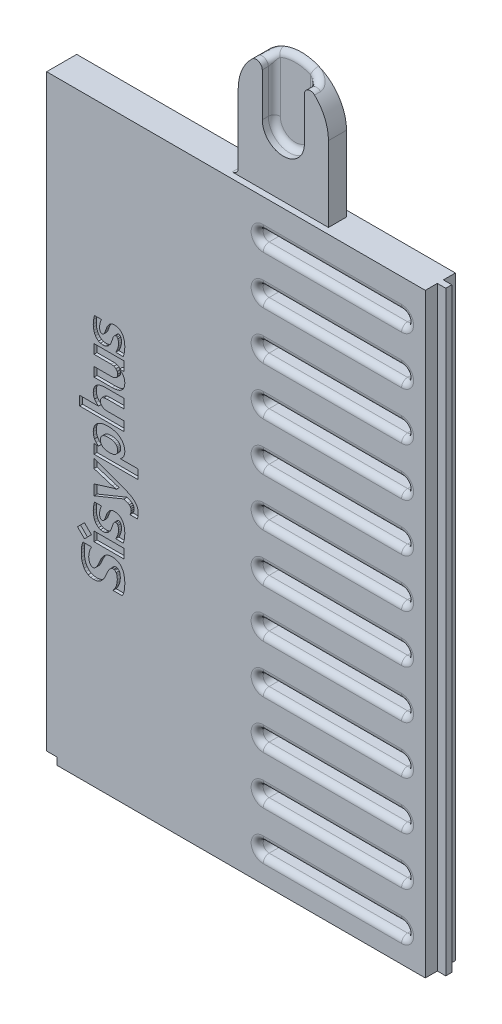
SolidWorks part; units mm, degrees
material "PVC Rigid"
ref_plane "Front Plane" through (0, 0, 0) normal (0, 0, 1) x (1, 0, 0)
ref_plane "Top Plane" through (0, 0, 0) normal (0, 1, 0) x (1, 0, 0)
ref_plane "Right Plane" through (0, 0, 0) normal (1, 0, 0) x (0, 0, -1)
sketch "Sketch1" plane through (0, 0, 0) normal (0, 1, 0) x (1, 0, 0)
  line L1 (-38.35, 2.5) -> (38.35, 2.5)
  line L2 (-38.35, 2.5) -> (-38.35, -2.5)
  line L3 (-38.35, -2.5) -> (38.35, -2.5)
  line L4 (38.35, 2.5) -> (38.35, -2.5)
  line L5 (-38.35, 2.5) -> (38.35, -2.5) construction
  line L6 (-38.35, -2.5) -> (38.35, 2.5) construction
  point P0 (0, 0)
  dimension "D1" = 5
  dimension "D2" = 76.7
extrude "Boss-Extrude1" add sketch "Sketch1" along normal blind 99
sketch "Sketch2" plane through (0, 99, 0) normal (0, 1, 0) x (1, 0, 0)
  line L0 (-7.5, -1.5) -> (-7.5, -0.5)
  line L1 (-6.5, 1.5) -> (7.5, 1.5)
  line L2 (-7.5, 0.5) -> (-7.5, -0.5)
  line L3 (-6.5, -1.5) -> (7.5, -1.5)
  line L5 (-7.5, 1.5) -> (7.5, -1.5) construction
  line L6 (-7.5, -1.5) -> (7.5, 1.5) construction
  line L7 (-7.5, 1.5) -> (-6.5, 1.5)
  line L8 (-7.5, -1.5) -> (-6.5, -1.5)
  line L9 (7.5, 1.5) -> (7.5, -1.5)
  line L12 (-7.5, 0.5) -> (-7.5, 1.5)
  point P0 (0, 0)
  dimension "D1" = 15
  dimension "D2" = 3
extrude "Boss-Extrude2" add sketch "Sketch2" along normal blind 20
sketch "Sketch3" plane through (0, 0, 1.5) normal (0, 0, 1) x (1, 0, 0)
  line L0 (-7.5, 119) -> (7.5, 119) construction
  line L1 (-3.5, 119) -> (3.5, 119)
  line L2 (-3.5, 119) -> (-3.5, 109)
  line L4 (3.5, 119) -> (3.5, 109)
  line L5 (-7.5, 119) -> (-7.5, 99) construction
  arc A0 (-3.5, 109) -> (3.5, 109) centre (0, 109) ccw
  dimension "D3" = 7.5
  dimension "D1" = 7
  dimension "D2" = 10
fillet "Fillet2" radius 1 1 edges at (-7.5, 99, 0)
sketch "Sketch4" plane through (0, 99, 0) normal (0, 1, 0) x (1, 0, 0)
  line L4 (-36.15, 0.5653) -> (-38.65, 0.5653)
  line L5 (-36.15, -1.4347) -> (-36.15, 0.5653)
  line L6 (-38.65, -1.4347) -> (-36.15, -1.4347)
  line L7 (-38.65, 0.5653) -> (-38.65, -1.4347)
  line L8 (-36.15, 0.5653) -> (-38.65, 0.5653)
  line L9 (-36.15, -1.4347) -> (-36.15, 0.5653)
  line L10 (-38.65, -1.4347) -> (-36.15, -1.4347)
  line L11 (-38.65, 0.5653) -> (-38.65, -1.4347)
  dimension "D1" = 0
sketch "Sketch5" plane through (0, 0, 0) normal (0, 0, 1) x (1, 0, 0)
  line L1 (24.6, -5) -> (60, -5)
  line L2 (24.6, -5) -> (24.6, 130)
  line L3 (24.6, 130) -> (60, 130)
  line L4 (60, -5) -> (60, 130)
extrude "Trim_door_beside_fixed_buttons" cut sketch "Sketch5" along normal blind 20 from offset 10 offset against normal yes
sketch "Sketch6" plane through (0, 0, 0) normal (0, 0, 1) x (1, 0, 0)
  line L0 (-39, -1) -> (-36.6, -1)
  line L1 (-36.6, -1) -> (-36.6, 1.2)
  line L2 (-36.6, 1.2) -> (-39, 1.2)
  line L3 (-39, 1.2) -> (-39, -1)
extrude "Clear_original_end_corner" cut sketch "Sketch6" along normal blind 10 from offset 5 offset against normal yes
sketch "Sketch8" plane through (0, 0, 0) normal (0, 0, 1) x (1, 0, 0)
  line L0 (24, 0) -> (26, 0)
  line L1 (26, 0) -> (26, 99)
  line L2 (26, 99) -> (24, 99)
  line L3 (24, 99) -> (24, 0)
extrude "Dust_overlap_tongue" add sketch "Sketch8" along normal blind 1 from offset 0.5 offset against normal yes
sketch "Sketch11" plane through (0, 0, 0) normal (0, 0, 1) x (1, 0, 0)
  line L0 (-4.6719, 20) -> (-5.7969, 19.8938)
  line L1 (-5.7969, 19.8938) -> (-5.9531, 20.3813)
  line L2 (-5.9531, 20.3813) -> (-6.2094, 20.725)
  line L3 (-6.2094, 20.725) -> (-6.5719, 20.925)
  line L4 (-6.5719, 20.925) -> (-7.0469, 20.9875)
  line L5 (-7.0469, 20.9875) -> (-7.5344, 20.9313)
  line L6 (-7.5344, 20.9313) -> (-7.8844, 20.75)
  line L7 (-7.8844, 20.75) -> (-8.1031, 20.4938)
  line L8 (-8.1031, 20.4938) -> (-8.1719, 20.2)
  line L9 (-8.1719, 20.2) -> (-8.1406, 20.0125)
  line L10 (-8.1406, 20.0125) -> (-8.0531, 19.8563)
  line L11 (-8.0531, 19.8563) -> (-7.8906, 19.7188)
  line L12 (-7.8906, 19.7188) -> (-7.6344, 19.6063)
  line L13 (-7.6344, 19.6063) -> (-7.4969, 19.5625)
  line L14 (-7.4969, 19.5625) -> (-7.3031, 19.5063)
  line L15 (-7.3031, 19.5063) -> (-7.0406, 19.4375)
  line L16 (-7.0406, 19.4375) -> (-6.7094, 19.3563)
  line L17 (-6.7094, 19.3563) -> (-6.2781, 19.2313)
  line L18 (-6.2781, 19.2313) -> (-5.9156, 19.1)
  line L19 (-5.9156, 19.1) -> (-5.6281, 18.95)
  line L20 (-5.6281, 18.95) -> (-5.4031, 18.7875)
  line L21 (-5.4031, 18.7875) -> (-5.1719, 18.5375)
  line L22 (-5.1719, 18.5375) -> (-5.0094, 18.2625)
  line L23 (-5.0094, 18.2625) -> (-4.9094, 17.9625)
  line L24 (-4.9094, 17.9625) -> (-4.8781, 17.6375)
  line L25 (-4.8781, 17.6375) -> (-4.9406, 17.2125)
  line L26 (-4.9406, 17.2125) -> (-5.1281, 16.8188)
  line L27 (-5.1281, 16.8188) -> (-5.4281, 16.4813)
  line L28 (-5.4281, 16.4813) -> (-5.8406, 16.2375)
  line L29 (-5.8406, 16.2375) -> (-6.3594, 16.0875)
  line L30 (-6.3594, 16.0875) -> (-6.9656, 16.0375)
  line L31 (-6.9656, 16.0375) -> (-7.4719, 16.0688)
  line L32 (-7.4719, 16.0688) -> (-7.9094, 16.1563)
  line L33 (-7.9094, 16.1563) -> (-8.2844, 16.3063)
  line L34 (-8.2844, 16.3063) -> (-8.5906, 16.5125)
  line L35 (-8.5906, 16.5125) -> (-8.8281, 16.7688)
  line L36 (-8.8281, 16.7688) -> (-9.0094, 17.0625)
  line L37 (-9.0094, 17.0625) -> (-9.1156, 17.4)
  line L38 (-9.1156, 17.4) -> (-9.1594, 17.775)
  line L39 (-9.1594, 17.775) -> (-8.0031, 17.825)
  line L40 (-8.0031, 17.825) -> (-7.8906, 17.4438)
  line L41 (-7.8906, 17.4438) -> (-7.6906, 17.1875)
  line L42 (-7.6906, 17.1875) -> (-7.3781, 17.0438)
  line L43 (-7.3781, 17.0438) -> (-6.9531, 16.9938)
  line L44 (-6.9531, 16.9938) -> (-6.5094, 17.05)
  line L45 (-6.5094, 17.05) -> (-6.1656, 17.2063)
  line L46 (-6.1656, 17.2063) -> (-6.0281, 17.3625)
  line L47 (-6.0281, 17.3625) -> (-5.9844, 17.5563)
  line L48 (-5.9844, 17.5563) -> (-6.0281, 17.75)
  line L49 (-6.0281, 17.75) -> (-6.1531, 17.9063)
  line L50 (-6.1531, 17.9063) -> (-6.3031, 18)
  line L51 (-6.3031, 18) -> (-6.5281, 18.0938)
  line L52 (-6.5281, 18.0938) -> (-6.8344, 18.1875)
  line L53 (-6.8344, 18.1875) -> (-7.2156, 18.2875)
  line L54 (-7.2156, 18.2875) -> (-7.6094, 18.3938)
  line L55 (-7.6094, 18.3938) -> (-7.9531, 18.4938)
  line L56 (-7.9531, 18.4938) -> (-8.2344, 18.6)
  line L57 (-8.2344, 18.6) -> (-8.4656, 18.7)
  line L58 (-8.4656, 18.7) -> (-8.8281, 18.9563)
  line L59 (-8.8281, 18.9563) -> (-9.0969, 19.2813)
  line L60 (-9.0969, 19.2813) -> (-9.2719, 19.6938)
  line L61 (-9.2719, 19.6938) -> (-9.3281, 20.1938)
  line L62 (-9.3281, 20.1938) -> (-9.2594, 20.675)
  line L63 (-9.2594, 20.675) -> (-9.0531, 21.1188)
  line L64 (-9.0531, 21.1188) -> (-8.7219, 21.4938)
  line L65 (-8.7219, 21.4938) -> (-8.2781, 21.7563)
  line L66 (-8.2781, 21.7563) -> (-7.7156, 21.9125)
  line L67 (-7.7156, 21.9125) -> (-7.0344, 21.9625)
  line L68 (-7.0344, 21.9625) -> (-6.5219, 21.9313)
  line L69 (-6.5219, 21.9313) -> (-6.0719, 21.8375)
  line L70 (-6.0719, 21.8375) -> (-5.6906, 21.6813)
  line L71 (-5.6906, 21.6813) -> (-5.3656, 21.4625)
  line L72 (-5.3656, 21.4625) -> (-5.1031, 21.1875)
  line L73 (-5.1031, 21.1875) -> (-4.9031, 20.85)
  line L74 (-4.9031, 20.85) -> (-4.7594, 20.4563)
  line L75 (-4.7594, 20.4563) -> (-4.6719, 20)
  line L76 (-6.4512, 25.1523) -> (-6.4512, 24.1367)
  line L77 (-6.4512, 24.1367) -> (-7.5488, 24.1367)
  line L78 (-7.5488, 24.1367) -> (-7.5488, 25.1523)
  line L79 (-7.5488, 25.1523) -> (-6.4512, 25.1523)
  line L80 (-6.4512, 29.8633) -> (-6.4512, 25.7148)
  line L81 (-6.4512, 25.7148) -> (-7.5488, 25.7148)
  line L82 (-7.5488, 25.7148) -> (-7.5488, 29.8633)
  line L83 (-7.5488, 29.8633) -> (-6.4512, 29.8633)
  line L84 (-5.0625, 35.8938) -> (-6.1687, 35.725)
  line L85 (-6.1687, 35.725) -> (-6.275, 36.0062)
  line L86 (-6.275, 36.0062) -> (-6.45, 36.2125)
  line L87 (-6.45, 36.2125) -> (-6.7062, 36.3313)
  line L88 (-6.7062, 36.3313) -> (-7.0562, 36.375)
  line L89 (-7.0562, 36.375) -> (-7.425, 36.3375)
  line L90 (-7.425, 36.3375) -> (-7.6937, 36.2188)
  line L91 (-7.6937, 36.2188) -> (-7.8062, 36.0938)
  line L92 (-7.8062, 36.0938) -> (-7.8375, 35.925)
  line L93 (-7.8375, 35.925) -> (-7.7625, 35.7188)
  line L94 (-7.7625, 35.7188) -> (-7.625, 35.6438)
  line L95 (-7.625, 35.6438) -> (-7.3937, 35.575)
  line L96 (-7.3937, 35.575) -> (-6.7875, 35.4313)
  line L97 (-6.7875, 35.4313) -> (-6.3125, 35.2937)
  line L98 (-6.3125, 35.2937) -> (-5.95, 35.1625)
  line L99 (-5.95, 35.1625) -> (-5.7125, 35.0437)
  line L100 (-5.7125, 35.0437) -> (-5.4937, 34.8562)
  line L101 (-5.4937, 34.8562) -> (-5.3438, 34.6438)
  line L102 (-5.3438, 34.6438) -> (-5.25, 34.3875)
  line L103 (-5.25, 34.3875) -> (-5.2188, 34.1062)
  line L104 (-5.2188, 34.1062) -> (-5.2437, 33.85)
  line L105 (-5.2437, 33.85) -> (-5.325, 33.6125)
  line L106 (-5.325, 33.6125) -> (-5.4562, 33.3938)
  line L107 (-5.4562, 33.3938) -> (-5.6437, 33.2)
  line L108 (-5.6437, 33.2) -> (-5.8875, 33.0375)
  line L109 (-5.8875, 33.0375) -> (-6.1875, 32.925)
  line L110 (-6.1875, 32.925) -> (-6.5437, 32.8563)
  line L111 (-6.5437, 32.8563) -> (-6.9625, 32.8313)
  line L112 (-6.9625, 32.8313) -> (-7.3625, 32.85)
  line L113 (-7.3625, 32.85) -> (-7.7062, 32.9)
  line L114 (-7.7062, 32.9) -> (-8, 32.9875)
  line L115 (-8, 32.9875) -> (-8.2313, 33.1125)
  line L116 (-8.2313, 33.1125) -> (-8.5812, 33.4563)
  line L117 (-8.5812, 33.4563) -> (-8.8, 33.9313)
  line L118 (-8.8, 33.9313) -> (-7.7625, 34.125)
  line L119 (-7.7625, 34.125) -> (-7.6687, 33.9125)
  line L120 (-7.6687, 33.9125) -> (-7.5125, 33.75)
  line L121 (-7.5125, 33.75) -> (-7.2875, 33.6563)
  line L122 (-7.2875, 33.6563) -> (-6.9812, 33.625)
  line L123 (-6.9812, 33.625) -> (-6.6125, 33.6563)
  line L124 (-6.6125, 33.6563) -> (-6.3625, 33.7438)
  line L125 (-6.3625, 33.7438) -> (-6.2687, 33.8438)
  line L126 (-6.2687, 33.8438) -> (-6.2375, 33.9688)
  line L127 (-6.2375, 33.9688) -> (-6.2625, 34.075)
  line L128 (-6.2625, 34.075) -> (-6.3438, 34.1687)
  line L129 (-6.3438, 34.1687) -> (-6.4625, 34.225)
  line L130 (-6.4625, 34.225) -> (-6.675, 34.3)
  line L131 (-6.675, 34.3) -> (-6.9812, 34.3812)
  line L132 (-6.9812, 34.3812) -> (-7.375, 34.475)
  line L133 (-7.375, 34.475) -> (-7.7812, 34.5813)
  line L134 (-7.7812, 34.5813) -> (-8.1187, 34.6937)
  line L135 (-8.1187, 34.6937) -> (-8.3875, 34.825)
  line L136 (-8.3875, 34.825) -> (-8.5938, 34.9625)
  line L137 (-8.5938, 34.9625) -> (-8.7437, 35.125)
  line L138 (-8.7437, 35.125) -> (-8.85, 35.3125)
  line L139 (-8.85, 35.3125) -> (-8.9187, 35.5312)
  line L140 (-8.9187, 35.5312) -> (-8.9375, 35.7812)
  line L141 (-8.9375, 35.7812) -> (-8.9062, 36.0563)
  line L142 (-8.9062, 36.0563) -> (-8.8187, 36.3125)
  line L143 (-8.8187, 36.3125) -> (-8.6688, 36.5438)
  line L144 (-8.6688, 36.5438) -> (-8.4625, 36.7625)
  line L145 (-8.4625, 36.7625) -> (-8.1937, 36.9375)
  line L146 (-8.1937, 36.9375) -> (-7.875, 37.0687)
  line L147 (-7.875, 37.0687) -> (-7.4937, 37.1438)
  line L148 (-7.4937, 37.1438) -> (-7.0562, 37.1688)
  line L149 (-7.0562, 37.1688) -> (-6.65, 37.15)
  line L150 (-6.65, 37.15) -> (-6.2937, 37.0813)
  line L151 (-6.2937, 37.0813) -> (-5.9812, 36.975)
  line L152 (-5.9812, 36.975) -> (-5.7125, 36.825)
  line L153 (-5.7125, 36.825) -> (-5.4875, 36.6375)
  line L154 (-5.4875, 36.6375) -> (-5.3063, 36.425)
  line L155 (-5.3063, 36.425) -> (-5.1625, 36.175)
  line L156 (-5.1625, 36.175) -> (-5.0625, 35.8938)
  line L157 (-4.8656, 40.0813) -> (-6.0344, 40.0813)
  line L158 (-6.0344, 40.0813) -> (-7.0281, 43.0312)
  line L159 (-7.0281, 43.0312) -> (-7.9969, 40.0813)
  line L160 (-7.9969, 40.0813) -> (-9.1344, 40.0813)
  line L161 (-9.1344, 40.0813) -> (-7.6656, 44.075)
  line L162 (-7.6656, 44.075) -> (-7.4031, 44.8)
  line L163 (-7.4031, 44.8) -> (-7.2656, 45.1187)
  line L164 (-7.2656, 45.1187) -> (-7.1281, 45.3562)
  line L165 (-7.1281, 45.3562) -> (-6.9906, 45.5312)
  line L166 (-6.9906, 45.5312) -> (-6.8281, 45.6625)
  line L167 (-6.8281, 45.6625) -> (-6.6406, 45.7688)
  line L168 (-6.6406, 45.7688) -> (-6.4094, 45.85)
  line L169 (-6.4094, 45.85) -> (-5.8531, 45.9187)
  line L170 (-5.8531, 45.9187) -> (-5.2281, 45.85)
  line L171 (-5.2281, 45.85) -> (-5.1344, 44.9875)
  line L172 (-5.1344, 44.9875) -> (-5.5969, 45.0437)
  line L173 (-5.5969, 45.0437) -> (-5.9281, 44.9875)
  line L174 (-5.9281, 44.9875) -> (-6.1656, 44.8187)
  line L175 (-6.1656, 44.8187) -> (-6.3281, 44.5625)
  line L176 (-6.3281, 44.5625) -> (-6.4469, 44.2438)
  line L177 (-6.4469, 44.2438) -> (-4.8656, 40.0813)
  line L178 (-4.975, 48.1813) -> (-6, 48.1813)
  line L179 (-6, 48.1813) -> (-6, 48.7938)
  line L180 (-6, 48.7938) -> (-6.2313, 48.5125)
  line L181 (-6.2313, 48.5125) -> (-6.5375, 48.2875)
  line L182 (-6.5375, 48.2875) -> (-6.9, 48.1375)
  line L183 (-6.9, 48.1375) -> (-7.2938, 48.0875)
  line L184 (-7.2938, 48.0875) -> (-7.6438, 48.125)
  line L185 (-7.6438, 48.125) -> (-7.9625, 48.2313)
  line L186 (-7.9625, 48.2313) -> (-8.25, 48.4062)
  line L187 (-8.25, 48.4062) -> (-8.5187, 48.6562)
  line L188 (-8.5187, 48.6562) -> (-8.7375, 48.9688)
  line L189 (-8.7375, 48.9688) -> (-8.9, 49.3375)
  line L190 (-8.9, 49.3375) -> (-8.9938, 49.7562)
  line L191 (-8.9938, 49.7562) -> (-9.025, 50.2375)
  line L192 (-9.025, 50.2375) -> (-8.9938, 50.725)
  line L193 (-8.9938, 50.725) -> (-8.9, 51.1562)
  line L194 (-8.9, 51.1562) -> (-8.7375, 51.5312)
  line L195 (-8.7375, 51.5312) -> (-8.5187, 51.85)
  line L196 (-8.5187, 51.85) -> (-8.25, 52.1)
  line L197 (-8.25, 52.1) -> (-7.9563, 52.2812)
  line L198 (-7.9563, 52.2812) -> (-7.6375, 52.3875)
  line L199 (-7.6375, 52.3875) -> (-7.2875, 52.425)
  line L200 (-7.2875, 52.425) -> (-6.9563, 52.3938)
  line L201 (-6.9563, 52.3938) -> (-6.6625, 52.2875)
  line L202 (-6.6625, 52.2875) -> (-6.375, 52.1062)
  line L203 (-6.375, 52.1062) -> (-6.075, 51.8187)
  line L204 (-6.075, 51.8187) -> (-6.075, 53.9125)
  line L205 (-6.075, 53.9125) -> (-4.975, 53.9125)
  line L206 (-4.975, 53.9125) -> (-4.975, 48.1813)
  line L207 (-6.0625, 50.1875) -> (-6.0813, 50.5187)
  line L208 (-6.0813, 50.5187) -> (-6.1313, 50.8)
  line L209 (-6.1313, 50.8) -> (-6.2188, 51.0312)
  line L210 (-6.2188, 51.0312) -> (-6.3375, 51.2188)
  line L211 (-6.3375, 51.2188) -> (-6.4875, 51.3688)
  line L212 (-6.4875, 51.3688) -> (-6.65, 51.475)
  line L213 (-6.65, 51.475) -> (-6.825, 51.5375)
  line L214 (-6.825, 51.5375) -> (-7.0188, 51.5563)
  line L215 (-7.0188, 51.5563) -> (-7.2, 51.5375)
  line L216 (-7.2, 51.5375) -> (-7.3625, 51.4812)
  line L217 (-7.3625, 51.4812) -> (-7.65, 51.25)
  line L218 (-7.65, 51.25) -> (-7.7625, 51.0687)
  line L219 (-7.7625, 51.0687) -> (-7.8438, 50.8438)
  line L220 (-7.8438, 50.8438) -> (-7.8938, 50.5687)
  line L221 (-7.8938, 50.5687) -> (-7.9063, 50.2438)
  line L222 (-7.9063, 50.2438) -> (-7.8875, 49.9375)
  line L223 (-7.8875, 49.9375) -> (-7.8438, 49.675)
  line L224 (-7.8438, 49.675) -> (-7.7563, 49.4562)
  line L225 (-7.7563, 49.4562) -> (-7.6438, 49.275)
  line L226 (-7.6438, 49.275) -> (-7.5063, 49.1375)
  line L227 (-7.5063, 49.1375) -> (-7.35, 49.0375)
  line L228 (-7.35, 49.0375) -> (-7.1813, 48.975)
  line L229 (-7.1813, 48.975) -> (-6.9938, 48.9562)
  line L230 (-6.9938, 48.9562) -> (-6.8063, 48.975)
  line L231 (-6.8063, 48.975) -> (-6.6313, 49.0375)
  line L232 (-6.6313, 49.0375) -> (-6.4688, 49.1312)
  line L233 (-6.4688, 49.1312) -> (-6.3313, 49.2687)
  line L234 (-6.3313, 49.2687) -> (-6.1313, 49.6562)
  line L235 (-6.1313, 49.6562) -> (-6.0625, 50.1875)
  line L236 (-6.2063, 56.1375) -> (-6.2063, 58.2438)
  line L237 (-6.2063, 58.2438) -> (-6.4875, 57.975)
  line L238 (-6.4875, 57.975) -> (-6.7938, 57.775)
  line L239 (-6.7938, 57.775) -> (-7.1188, 57.6563)
  line L240 (-7.1188, 57.6563) -> (-7.475, 57.6188)
  line L241 (-7.475, 57.6188) -> (-7.8375, 57.6563)
  line L242 (-7.8375, 57.6563) -> (-8.1625, 57.7625)
  line L243 (-8.1625, 57.7625) -> (-8.4313, 57.925)
  line L244 (-8.4313, 57.925) -> (-8.6188, 58.1188)
  line L245 (-8.6188, 58.1188) -> (-8.75, 58.3563)
  line L246 (-8.75, 58.3563) -> (-8.8313, 58.6063)
  line L247 (-8.8313, 58.6063) -> (-8.875, 58.9438)
  line L248 (-8.875, 58.9438) -> (-8.8875, 59.4313)
  line L249 (-8.8875, 59.4313) -> (-8.8875, 61.8625)
  line L250 (-8.8875, 61.8625) -> (-7.7875, 61.8625)
  line L251 (-7.7875, 61.8625) -> (-7.7875, 59.675)
  line L252 (-7.7875, 59.675) -> (-7.7813, 59.375)
  line L253 (-7.7813, 59.375) -> (-7.775, 59.1375)
  line L254 (-7.775, 59.1375) -> (-7.7563, 58.9625)
  line L255 (-7.7563, 58.9625) -> (-7.725, 58.8438)
  line L256 (-7.725, 58.8438) -> (-7.6438, 58.6875)
  line L257 (-7.6438, 58.6875) -> (-7.5063, 58.5625)
  line L258 (-7.5063, 58.5625) -> (-7.3313, 58.4875)
  line L259 (-7.3313, 58.4875) -> (-7.1125, 58.4625)
  line L260 (-7.1125, 58.4625) -> (-6.8563, 58.4938)
  line L261 (-6.8563, 58.4938) -> (-6.625, 58.5938)
  line L262 (-6.625, 58.5938) -> (-6.4375, 58.7625)
  line L263 (-6.4375, 58.7625) -> (-6.3063, 58.9938)
  line L264 (-6.3063, 58.9938) -> (-6.2313, 59.325)
  line L265 (-6.2313, 59.325) -> (-6.2063, 59.7875)
  line L266 (-6.2063, 59.7875) -> (-6.2063, 61.8625)
  line L267 (-6.2063, 61.8625) -> (-5.1125, 61.8625)
  line L268 (-5.1125, 61.8625) -> (-5.1125, 56.1375)
  line L269 (-5.1125, 56.1375) -> (-6.2063, 56.1375)
  line L270 (-7.8656, 69.0281) -> (-7.8656, 68.4094)
  line L271 (-7.8656, 68.4094) -> (-7.6031, 68.7031)
  line L272 (-7.6031, 68.7031) -> (-7.2719, 68.9344)
  line L273 (-7.2719, 68.9344) -> (-6.8906, 69.0781)
  line L274 (-6.8906, 69.0781) -> (-6.4906, 69.1219)
  line L275 (-6.4906, 69.1219) -> (-6.0969, 69.0781)
  line L276 (-6.0969, 69.0781) -> (-5.7406, 68.9406)
  line L277 (-5.7406, 68.9406) -> (-5.4531, 68.7219)
  line L278 (-5.4531, 68.7219) -> (-5.2594, 68.4219)
  line L279 (-5.2594, 68.4219) -> (-5.1531, 68.0281)
  line L280 (-5.1531, 68.0281) -> (-5.1156, 67.5031)
  line L281 (-5.1156, 67.5031) -> (-5.1156, 64.8781)
  line L282 (-5.1156, 64.8781) -> (-6.2094, 64.8781)
  line L283 (-6.2094, 64.8781) -> (-6.2094, 66.7844)
  line L284 (-6.2094, 66.7844) -> (-6.2156, 67.1844)
  line L285 (-6.2156, 67.1844) -> (-6.2219, 67.4906)
  line L286 (-6.2219, 67.4906) -> (-6.2406, 67.7156)
  line L287 (-6.2406, 67.7156) -> (-6.2719, 67.8594)
  line L288 (-6.2719, 67.8594) -> (-6.3531, 68.0344)
  line L289 (-6.3531, 68.0344) -> (-6.4906, 68.1719)
  line L290 (-6.4906, 68.1719) -> (-6.6719, 68.2594)
  line L291 (-6.6719, 68.2594) -> (-6.8969, 68.2844)
  line L292 (-6.8969, 68.2844) -> (-7.1656, 68.2469)
  line L293 (-7.1656, 68.2469) -> (-7.4031, 68.1344)
  line L294 (-7.4031, 68.1344) -> (-7.5906, 67.9594)
  line L295 (-7.5906, 67.9594) -> (-7.7094, 67.7531)
  line L296 (-7.7094, 67.7531) -> (-7.7406, 67.5969)
  line L297 (-7.7406, 67.5969) -> (-7.7719, 67.3531)
  line L298 (-7.7719, 67.3531) -> (-7.7844, 67.0344)
  line L299 (-7.7844, 67.0344) -> (-7.7906, 66.6281)
  line L300 (-7.7906, 66.6281) -> (-7.7906, 64.8781)
  line L301 (-7.7906, 64.8781) -> (-8.8844, 64.8781)
  line L302 (-8.8844, 64.8781) -> (-8.8844, 69.0281)
  line L303 (-8.8844, 69.0281) -> (-7.8656, 69.0281)
  line L304 (-5.0625, 75.8938) -> (-6.1687, 75.725)
  line L305 (-6.1687, 75.725) -> (-6.275, 76.0062)
  line L306 (-6.275, 76.0062) -> (-6.45, 76.2125)
  line L307 (-6.45, 76.2125) -> (-6.7062, 76.3313)
  line L308 (-6.7062, 76.3313) -> (-7.0562, 76.375)
  line L309 (-7.0562, 76.375) -> (-7.425, 76.3375)
  line L310 (-7.425, 76.3375) -> (-7.6937, 76.2188)
  line L311 (-7.6937, 76.2188) -> (-7.8062, 76.0938)
  line L312 (-7.8062, 76.0938) -> (-7.8375, 75.925)
  line L313 (-7.8375, 75.925) -> (-7.7625, 75.7188)
  line L314 (-7.7625, 75.7188) -> (-7.625, 75.6438)
  line L315 (-7.625, 75.6438) -> (-7.3937, 75.575)
  line L316 (-7.3937, 75.575) -> (-6.7875, 75.4313)
  line L317 (-6.7875, 75.4313) -> (-6.3125, 75.2937)
  line L318 (-6.3125, 75.2937) -> (-5.95, 75.1625)
  line L319 (-5.95, 75.1625) -> (-5.7125, 75.0437)
  line L320 (-5.7125, 75.0437) -> (-5.4937, 74.8562)
  line L321 (-5.4937, 74.8562) -> (-5.3438, 74.6438)
  line L322 (-5.3438, 74.6438) -> (-5.25, 74.3875)
  line L323 (-5.25, 74.3875) -> (-5.2188, 74.1062)
  line L324 (-5.2188, 74.1062) -> (-5.2437, 73.85)
  line L325 (-5.2437, 73.85) -> (-5.325, 73.6125)
  line L326 (-5.325, 73.6125) -> (-5.4562, 73.3938)
  line L327 (-5.4562, 73.3938) -> (-5.6437, 73.2)
  line L328 (-5.6437, 73.2) -> (-5.8875, 73.0375)
  line L329 (-5.8875, 73.0375) -> (-6.1875, 72.925)
  line L330 (-6.1875, 72.925) -> (-6.5437, 72.8563)
  line L331 (-6.5437, 72.8563) -> (-6.9625, 72.8313)
  line L332 (-6.9625, 72.8313) -> (-7.3625, 72.85)
  line L333 (-7.3625, 72.85) -> (-7.7062, 72.9)
  line L334 (-7.7062, 72.9) -> (-8, 72.9875)
  line L335 (-8, 72.9875) -> (-8.2313, 73.1125)
  line L336 (-8.2313, 73.1125) -> (-8.5812, 73.4563)
  line L337 (-8.5812, 73.4563) -> (-8.8, 73.9313)
  line L338 (-8.8, 73.9313) -> (-7.7625, 74.125)
  line L339 (-7.7625, 74.125) -> (-7.6687, 73.9125)
  line L340 (-7.6687, 73.9125) -> (-7.5125, 73.75)
  line L341 (-7.5125, 73.75) -> (-7.2875, 73.6563)
  line L342 (-7.2875, 73.6563) -> (-6.9812, 73.625)
  line L343 (-6.9812, 73.625) -> (-6.6125, 73.6563)
  line L344 (-6.6125, 73.6563) -> (-6.3625, 73.7438)
  line L345 (-6.3625, 73.7438) -> (-6.2687, 73.8438)
  line L346 (-6.2687, 73.8438) -> (-6.2375, 73.9688)
  line L347 (-6.2375, 73.9688) -> (-6.2625, 74.075)
  line L348 (-6.2625, 74.075) -> (-6.3438, 74.1687)
  line L349 (-6.3438, 74.1687) -> (-6.4625, 74.225)
  line L350 (-6.4625, 74.225) -> (-6.675, 74.3)
  line L351 (-6.675, 74.3) -> (-6.9812, 74.3812)
  line L352 (-6.9812, 74.3812) -> (-7.375, 74.475)
  line L353 (-7.375, 74.475) -> (-7.7812, 74.5813)
  line L354 (-7.7812, 74.5813) -> (-8.1187, 74.6937)
  line L355 (-8.1187, 74.6937) -> (-8.3875, 74.825)
  line L356 (-8.3875, 74.825) -> (-8.5938, 74.9625)
  line L357 (-8.5938, 74.9625) -> (-8.7437, 75.125)
  line L358 (-8.7437, 75.125) -> (-8.85, 75.3125)
  line L359 (-8.85, 75.3125) -> (-8.9187, 75.5312)
  line L360 (-8.9187, 75.5312) -> (-8.9375, 75.7812)
  line L361 (-8.9375, 75.7812) -> (-8.9062, 76.0563)
  line L362 (-8.9062, 76.0563) -> (-8.8187, 76.3125)
  line L363 (-8.8187, 76.3125) -> (-8.6688, 76.5438)
  line L364 (-8.6688, 76.5438) -> (-8.4625, 76.7625)
  line L365 (-8.4625, 76.7625) -> (-8.1937, 76.9375)
  line L366 (-8.1937, 76.9375) -> (-7.875, 77.0687)
  line L367 (-7.875, 77.0687) -> (-7.4937, 77.1438)
  line L368 (-7.4937, 77.1438) -> (-7.0562, 77.1688)
  line L369 (-7.0562, 77.1688) -> (-6.65, 77.15)
  line L370 (-6.65, 77.15) -> (-6.2937, 77.0813)
  line L371 (-6.2937, 77.0813) -> (-5.9812, 76.975)
  line L372 (-5.9812, 76.975) -> (-5.7125, 76.825)
  line L373 (-5.7125, 76.825) -> (-5.4875, 76.6375)
  line L374 (-5.4875, 76.6375) -> (-5.3063, 76.425)
  line L375 (-5.3063, 76.425) -> (-5.1625, 76.175)
  line L376 (-5.1625, 76.175) -> (-5.0625, 75.8938)
extrude "Sisyphus_vertical_engraving_0p5mm" [suppressed] cut sketch "Sketch11" along normal blind 1 from offset 2
sketch "Sketch12" plane through (0, 0, 0) normal (0, 0, 1) x (1, 0, 0)
  line L0 (-9.3281, 74) -> (-8.2031, 74.1062)
  line L1 (-8.2031, 74.1062) -> (-8.0469, 73.6187)
  line L2 (-8.0469, 73.6187) -> (-7.7906, 73.275)
  line L3 (-7.7906, 73.275) -> (-7.4281, 73.075)
  line L4 (-7.4281, 73.075) -> (-6.9531, 73.0125)
  line L5 (-6.9531, 73.0125) -> (-6.4656, 73.0687)
  line L6 (-6.4656, 73.0687) -> (-6.1156, 73.25)
  line L7 (-6.1156, 73.25) -> (-5.8969, 73.5062)
  line L8 (-5.8969, 73.5062) -> (-5.8281, 73.8)
  line L9 (-5.8281, 73.8) -> (-5.8594, 73.9875)
  line L10 (-5.8594, 73.9875) -> (-5.9469, 74.1437)
  line L11 (-5.9469, 74.1437) -> (-6.1094, 74.2812)
  line L12 (-6.1094, 74.2812) -> (-6.3656, 74.3937)
  line L13 (-6.3656, 74.3937) -> (-6.5031, 74.4375)
  line L14 (-6.5031, 74.4375) -> (-6.6969, 74.4937)
  line L15 (-6.6969, 74.4937) -> (-6.9594, 74.5625)
  line L16 (-6.9594, 74.5625) -> (-7.2906, 74.6437)
  line L17 (-7.2906, 74.6437) -> (-7.7219, 74.7687)
  line L18 (-7.7219, 74.7687) -> (-8.0844, 74.9)
  line L19 (-8.0844, 74.9) -> (-8.3719, 75.05)
  line L20 (-8.3719, 75.05) -> (-8.5969, 75.2125)
  line L21 (-8.5969, 75.2125) -> (-8.8281, 75.4625)
  line L22 (-8.8281, 75.4625) -> (-8.9906, 75.7375)
  line L23 (-8.9906, 75.7375) -> (-9.0906, 76.0375)
  line L24 (-9.0906, 76.0375) -> (-9.1219, 76.3625)
  line L25 (-9.1219, 76.3625) -> (-9.0594, 76.7875)
  line L26 (-9.0594, 76.7875) -> (-8.8719, 77.1812)
  line L27 (-8.8719, 77.1812) -> (-8.5719, 77.5187)
  line L28 (-8.5719, 77.5187) -> (-8.1594, 77.7625)
  line L29 (-8.1594, 77.7625) -> (-7.6406, 77.9125)
  line L30 (-7.6406, 77.9125) -> (-7.0344, 77.9625)
  line L31 (-7.0344, 77.9625) -> (-6.5281, 77.9312)
  line L32 (-6.5281, 77.9312) -> (-6.0906, 77.8437)
  line L33 (-6.0906, 77.8437) -> (-5.7156, 77.6937)
  line L34 (-5.7156, 77.6937) -> (-5.4094, 77.4875)
  line L35 (-5.4094, 77.4875) -> (-5.1719, 77.2312)
  line L36 (-5.1719, 77.2312) -> (-4.9906, 76.9375)
  line L37 (-4.9906, 76.9375) -> (-4.8844, 76.6)
  line L38 (-4.8844, 76.6) -> (-4.8406, 76.225)
  line L39 (-4.8406, 76.225) -> (-5.9969, 76.175)
  line L40 (-5.9969, 76.175) -> (-6.1094, 76.5562)
  line L41 (-6.1094, 76.5562) -> (-6.3094, 76.8125)
  line L42 (-6.3094, 76.8125) -> (-6.6219, 76.9562)
  line L43 (-6.6219, 76.9562) -> (-7.0469, 77.0062)
  line L44 (-7.0469, 77.0062) -> (-7.4906, 76.95)
  line L45 (-7.4906, 76.95) -> (-7.8344, 76.7937)
  line L46 (-7.8344, 76.7937) -> (-7.9719, 76.6375)
  line L47 (-7.9719, 76.6375) -> (-8.0156, 76.4437)
  line L48 (-8.0156, 76.4437) -> (-7.9719, 76.25)
  line L49 (-7.9719, 76.25) -> (-7.8469, 76.0937)
  line L50 (-7.8469, 76.0937) -> (-7.6969, 76)
  line L51 (-7.6969, 76) -> (-7.4719, 75.9062)
  line L52 (-7.4719, 75.9062) -> (-7.1656, 75.8125)
  line L53 (-7.1656, 75.8125) -> (-6.7844, 75.7125)
  line L54 (-6.7844, 75.7125) -> (-6.3906, 75.6062)
  line L55 (-6.3906, 75.6062) -> (-6.0469, 75.5062)
  line L56 (-6.0469, 75.5062) -> (-5.7656, 75.4)
  line L57 (-5.7656, 75.4) -> (-5.5344, 75.3)
  line L58 (-5.5344, 75.3) -> (-5.1719, 75.0437)
  line L59 (-5.1719, 75.0437) -> (-4.9031, 74.7187)
  line L60 (-4.9031, 74.7187) -> (-4.7281, 74.3062)
  line L61 (-4.7281, 74.3062) -> (-4.6719, 73.8062)
  line L62 (-4.6719, 73.8062) -> (-4.7406, 73.325)
  line L63 (-4.7406, 73.325) -> (-4.9469, 72.8812)
  line L64 (-4.9469, 72.8812) -> (-5.2781, 72.5062)
  line L65 (-5.2781, 72.5062) -> (-5.7219, 72.2437)
  line L66 (-5.7219, 72.2437) -> (-6.2844, 72.0875)
  line L67 (-6.2844, 72.0875) -> (-6.9656, 72.0375)
  line L68 (-6.9656, 72.0375) -> (-7.4781, 72.0687)
  line L69 (-7.4781, 72.0687) -> (-7.9281, 72.1625)
  line L70 (-7.9281, 72.1625) -> (-8.3094, 72.3187)
  line L71 (-8.3094, 72.3187) -> (-8.6344, 72.5375)
  line L72 (-8.6344, 72.5375) -> (-8.8969, 72.8125)
  line L73 (-8.8969, 72.8125) -> (-9.0969, 73.15)
  line L74 (-9.0969, 73.15) -> (-9.2406, 73.5437)
  line L75 (-9.2406, 73.5437) -> (-9.3281, 74)
  line L76 (-7.5488, 68.8477) -> (-7.5488, 69.8633)
  line L77 (-7.5488, 69.8633) -> (-6.4512, 69.8633)
  line L78 (-6.4512, 69.8633) -> (-6.4512, 68.8477)
  line L79 (-6.4512, 68.8477) -> (-7.5488, 68.8477)
  line L80 (-7.5488, 64.1367) -> (-7.5488, 68.2852)
  line L81 (-7.5488, 68.2852) -> (-6.4512, 68.2852)
  line L82 (-6.4512, 68.2852) -> (-6.4512, 64.1367)
  line L83 (-6.4512, 64.1367) -> (-7.5488, 64.1367)
  line L84 (-8.9375, 58.1062) -> (-7.8313, 58.275)
  line L85 (-7.8313, 58.275) -> (-7.725, 57.9938)
  line L86 (-7.725, 57.9938) -> (-7.55, 57.7875)
  line L87 (-7.55, 57.7875) -> (-7.2938, 57.6687)
  line L88 (-7.2938, 57.6687) -> (-6.9438, 57.625)
  line L89 (-6.9438, 57.625) -> (-6.575, 57.6625)
  line L90 (-6.575, 57.6625) -> (-6.3063, 57.7812)
  line L91 (-6.3063, 57.7812) -> (-6.1938, 57.9062)
  line L92 (-6.1938, 57.9062) -> (-6.1625, 58.075)
  line L93 (-6.1625, 58.075) -> (-6.2375, 58.2812)
  line L94 (-6.2375, 58.2812) -> (-6.375, 58.3562)
  line L95 (-6.375, 58.3562) -> (-6.6063, 58.425)
  line L96 (-6.6063, 58.425) -> (-7.2125, 58.5687)
  line L97 (-7.2125, 58.5687) -> (-7.6875, 58.7063)
  line L98 (-7.6875, 58.7063) -> (-8.05, 58.8375)
  line L99 (-8.05, 58.8375) -> (-8.2875, 58.9563)
  line L100 (-8.2875, 58.9563) -> (-8.5063, 59.1438)
  line L101 (-8.5063, 59.1438) -> (-8.6562, 59.3562)
  line L102 (-8.6562, 59.3562) -> (-8.75, 59.6125)
  line L103 (-8.75, 59.6125) -> (-8.7812, 59.8938)
  line L104 (-8.7812, 59.8938) -> (-8.7563, 60.15)
  line L105 (-8.7563, 60.15) -> (-8.675, 60.3875)
  line L106 (-8.675, 60.3875) -> (-8.5438, 60.6062)
  line L107 (-8.5438, 60.6062) -> (-8.3563, 60.8)
  line L108 (-8.3563, 60.8) -> (-8.1125, 60.9625)
  line L109 (-8.1125, 60.9625) -> (-7.8125, 61.075)
  line L110 (-7.8125, 61.075) -> (-7.4563, 61.1437)
  line L111 (-7.4563, 61.1437) -> (-7.0375, 61.1687)
  line L112 (-7.0375, 61.1687) -> (-6.6375, 61.15)
  line L113 (-6.6375, 61.15) -> (-6.2938, 61.1)
  line L114 (-6.2938, 61.1) -> (-6, 61.0125)
  line L115 (-6, 61.0125) -> (-5.7687, 60.8875)
  line L116 (-5.7687, 60.8875) -> (-5.4188, 60.5437)
  line L117 (-5.4188, 60.5437) -> (-5.2, 60.0687)
  line L118 (-5.2, 60.0687) -> (-6.2375, 59.875)
  line L119 (-6.2375, 59.875) -> (-6.3313, 60.0875)
  line L120 (-6.3313, 60.0875) -> (-6.4875, 60.25)
  line L121 (-6.4875, 60.25) -> (-6.7125, 60.3437)
  line L122 (-6.7125, 60.3437) -> (-7.0188, 60.375)
  line L123 (-7.0188, 60.375) -> (-7.3875, 60.3437)
  line L124 (-7.3875, 60.3437) -> (-7.6375, 60.2562)
  line L125 (-7.6375, 60.2562) -> (-7.7313, 60.1562)
  line L126 (-7.7313, 60.1562) -> (-7.7625, 60.0312)
  line L127 (-7.7625, 60.0312) -> (-7.7375, 59.925)
  line L128 (-7.7375, 59.925) -> (-7.6562, 59.8313)
  line L129 (-7.6562, 59.8313) -> (-7.5375, 59.775)
  line L130 (-7.5375, 59.775) -> (-7.325, 59.7)
  line L131 (-7.325, 59.7) -> (-7.0188, 59.6188)
  line L132 (-7.0188, 59.6188) -> (-6.625, 59.525)
  line L133 (-6.625, 59.525) -> (-6.2188, 59.4187)
  line L134 (-6.2188, 59.4187) -> (-5.8813, 59.3063)
  line L135 (-5.8813, 59.3063) -> (-5.6125, 59.175)
  line L136 (-5.6125, 59.175) -> (-5.4062, 59.0375)
  line L137 (-5.4062, 59.0375) -> (-5.2563, 58.875)
  line L138 (-5.2563, 58.875) -> (-5.15, 58.6875)
  line L139 (-5.15, 58.6875) -> (-5.0813, 58.4688)
  line L140 (-5.0813, 58.4688) -> (-5.0625, 58.2188)
  line L141 (-5.0625, 58.2188) -> (-5.0938, 57.9437)
  line L142 (-5.0938, 57.9437) -> (-5.1813, 57.6875)
  line L143 (-5.1813, 57.6875) -> (-5.3312, 57.4562)
  line L144 (-5.3312, 57.4562) -> (-5.5375, 57.2375)
  line L145 (-5.5375, 57.2375) -> (-5.8063, 57.0625)
  line L146 (-5.8063, 57.0625) -> (-6.125, 56.9313)
  line L147 (-6.125, 56.9313) -> (-6.5063, 56.8562)
  line L148 (-6.5063, 56.8562) -> (-6.9438, 56.8312)
  line L149 (-6.9438, 56.8312) -> (-7.35, 56.85)
  line L150 (-7.35, 56.85) -> (-7.7063, 56.9187)
  line L151 (-7.7063, 56.9187) -> (-8.0188, 57.025)
  line L152 (-8.0188, 57.025) -> (-8.2875, 57.175)
  line L153 (-8.2875, 57.175) -> (-8.5125, 57.3625)
  line L154 (-8.5125, 57.3625) -> (-8.6937, 57.575)
  line L155 (-8.6937, 57.575) -> (-8.8375, 57.825)
  line L156 (-8.8375, 57.825) -> (-8.9375, 58.1062)
  line L157 (-9.1344, 53.9187) -> (-7.9656, 53.9187)
  line L158 (-7.9656, 53.9187) -> (-6.9719, 50.9688)
  line L159 (-6.9719, 50.9688) -> (-6.0031, 53.9187)
  line L160 (-6.0031, 53.9187) -> (-4.8656, 53.9187)
  line L161 (-4.8656, 53.9187) -> (-6.3344, 49.925)
  line L162 (-6.3344, 49.925) -> (-6.5969, 49.2)
  line L163 (-6.5969, 49.2) -> (-6.7344, 48.8813)
  line L164 (-6.7344, 48.8813) -> (-6.8719, 48.6438)
  line L165 (-6.8719, 48.6438) -> (-7.0094, 48.4688)
  line L166 (-7.0094, 48.4688) -> (-7.1719, 48.3375)
  line L167 (-7.1719, 48.3375) -> (-7.3594, 48.2312)
  line L168 (-7.3594, 48.2312) -> (-7.5906, 48.15)
  line L169 (-7.5906, 48.15) -> (-8.1469, 48.0813)
  line L170 (-8.1469, 48.0813) -> (-8.7719, 48.15)
  line L171 (-8.7719, 48.15) -> (-8.8656, 49.0125)
  line L172 (-8.8656, 49.0125) -> (-8.4031, 48.9563)
  line L173 (-8.4031, 48.9563) -> (-8.0719, 49.0125)
  line L174 (-8.0719, 49.0125) -> (-7.8344, 49.1813)
  line L175 (-7.8344, 49.1813) -> (-7.6719, 49.4375)
  line L176 (-7.6719, 49.4375) -> (-7.5531, 49.7562)
  line L177 (-7.5531, 49.7562) -> (-9.1344, 53.9187)
  line L178 (-9.025, 45.8187) -> (-8, 45.8187)
  line L179 (-8, 45.8187) -> (-8, 45.2062)
  line L180 (-8, 45.2062) -> (-7.7687, 45.4875)
  line L181 (-7.7687, 45.4875) -> (-7.4625, 45.7125)
  line L182 (-7.4625, 45.7125) -> (-7.1, 45.8625)
  line L183 (-7.1, 45.8625) -> (-6.7062, 45.9125)
  line L184 (-6.7062, 45.9125) -> (-6.3562, 45.875)
  line L185 (-6.3562, 45.875) -> (-6.0375, 45.7687)
  line L186 (-6.0375, 45.7687) -> (-5.75, 45.5938)
  line L187 (-5.75, 45.5938) -> (-5.4813, 45.3438)
  line L188 (-5.4813, 45.3438) -> (-5.2625, 45.0312)
  line L189 (-5.2625, 45.0312) -> (-5.1, 44.6625)
  line L190 (-5.1, 44.6625) -> (-5.0062, 44.2438)
  line L191 (-5.0062, 44.2438) -> (-4.975, 43.7625)
  line L192 (-4.975, 43.7625) -> (-5.0062, 43.275)
  line L193 (-5.0062, 43.275) -> (-5.1, 42.8438)
  line L194 (-5.1, 42.8438) -> (-5.2625, 42.4688)
  line L195 (-5.2625, 42.4688) -> (-5.4813, 42.15)
  line L196 (-5.4813, 42.15) -> (-5.75, 41.9)
  line L197 (-5.75, 41.9) -> (-6.0437, 41.7188)
  line L198 (-6.0437, 41.7188) -> (-6.3625, 41.6125)
  line L199 (-6.3625, 41.6125) -> (-6.7125, 41.575)
  line L200 (-6.7125, 41.575) -> (-7.0437, 41.6062)
  line L201 (-7.0437, 41.6062) -> (-7.3375, 41.7125)
  line L202 (-7.3375, 41.7125) -> (-7.625, 41.8938)
  line L203 (-7.625, 41.8938) -> (-7.925, 42.1813)
  line L204 (-7.925, 42.1813) -> (-7.925, 40.0875)
  line L205 (-7.925, 40.0875) -> (-9.025, 40.0875)
  line L206 (-9.025, 40.0875) -> (-9.025, 45.8187)
  line L207 (-7.9375, 43.8125) -> (-7.9187, 43.4813)
  line L208 (-7.9187, 43.4813) -> (-7.8687, 43.2)
  line L209 (-7.8687, 43.2) -> (-7.7812, 42.9688)
  line L210 (-7.7812, 42.9688) -> (-7.6625, 42.7812)
  line L211 (-7.6625, 42.7812) -> (-7.5125, 42.6312)
  line L212 (-7.5125, 42.6312) -> (-7.35, 42.525)
  line L213 (-7.35, 42.525) -> (-7.175, 42.4625)
  line L214 (-7.175, 42.4625) -> (-6.9812, 42.4437)
  line L215 (-6.9812, 42.4437) -> (-6.8, 42.4625)
  line L216 (-6.8, 42.4625) -> (-6.6375, 42.5188)
  line L217 (-6.6375, 42.5188) -> (-6.35, 42.75)
  line L218 (-6.35, 42.75) -> (-6.2375, 42.9313)
  line L219 (-6.2375, 42.9313) -> (-6.1562, 43.1562)
  line L220 (-6.1562, 43.1562) -> (-6.1062, 43.4313)
  line L221 (-6.1062, 43.4313) -> (-6.0937, 43.7562)
  line L222 (-6.0937, 43.7562) -> (-6.1125, 44.0625)
  line L223 (-6.1125, 44.0625) -> (-6.1562, 44.325)
  line L224 (-6.1562, 44.325) -> (-6.2437, 44.5438)
  line L225 (-6.2437, 44.5438) -> (-6.3562, 44.725)
  line L226 (-6.3562, 44.725) -> (-6.4937, 44.8625)
  line L227 (-6.4937, 44.8625) -> (-6.65, 44.9625)
  line L228 (-6.65, 44.9625) -> (-6.8187, 45.025)
  line L229 (-6.8187, 45.025) -> (-7.0062, 45.0438)
  line L230 (-7.0062, 45.0438) -> (-7.1937, 45.025)
  line L231 (-7.1937, 45.025) -> (-7.3687, 44.9625)
  line L232 (-7.3687, 44.9625) -> (-7.5312, 44.8688)
  line L233 (-7.5312, 44.8688) -> (-7.6687, 44.7313)
  line L234 (-7.6687, 44.7313) -> (-7.8687, 44.3438)
  line L235 (-7.8687, 44.3438) -> (-7.9375, 43.8125)
  line L236 (-7.7937, 37.8625) -> (-7.7937, 35.7562)
  line L237 (-7.7937, 35.7562) -> (-7.5125, 36.025)
  line L238 (-7.5125, 36.025) -> (-7.2062, 36.225)
  line L239 (-7.2062, 36.225) -> (-6.8812, 36.3437)
  line L240 (-6.8812, 36.3437) -> (-6.525, 36.3812)
  line L241 (-6.525, 36.3812) -> (-6.1625, 36.3437)
  line L242 (-6.1625, 36.3437) -> (-5.8375, 36.2375)
  line L243 (-5.8375, 36.2375) -> (-5.5687, 36.075)
  line L244 (-5.5687, 36.075) -> (-5.3812, 35.8812)
  line L245 (-5.3812, 35.8812) -> (-5.25, 35.6437)
  line L246 (-5.25, 35.6437) -> (-5.1687, 35.3937)
  line L247 (-5.1687, 35.3937) -> (-5.125, 35.0562)
  line L248 (-5.125, 35.0562) -> (-5.1125, 34.5687)
  line L249 (-5.1125, 34.5687) -> (-5.1125, 32.1375)
  line L250 (-5.1125, 32.1375) -> (-6.2125, 32.1375)
  line L251 (-6.2125, 32.1375) -> (-6.2125, 34.325)
  line L252 (-6.2125, 34.325) -> (-6.2187, 34.625)
  line L253 (-6.2187, 34.625) -> (-6.225, 34.8625)
  line L254 (-6.225, 34.8625) -> (-6.2437, 35.0375)
  line L255 (-6.2437, 35.0375) -> (-6.275, 35.1562)
  line L256 (-6.275, 35.1562) -> (-6.3562, 35.3125)
  line L257 (-6.3562, 35.3125) -> (-6.4937, 35.4375)
  line L258 (-6.4937, 35.4375) -> (-6.6687, 35.5125)
  line L259 (-6.6687, 35.5125) -> (-6.8875, 35.5375)
  line L260 (-6.8875, 35.5375) -> (-7.1437, 35.5062)
  line L261 (-7.1437, 35.5062) -> (-7.375, 35.4062)
  line L262 (-7.375, 35.4062) -> (-7.5625, 35.2375)
  line L263 (-7.5625, 35.2375) -> (-7.6937, 35.0062)
  line L264 (-7.6937, 35.0062) -> (-7.7687, 34.675)
  line L265 (-7.7687, 34.675) -> (-7.7937, 34.2125)
  line L266 (-7.7937, 34.2125) -> (-7.7937, 32.1375)
  line L267 (-7.7937, 32.1375) -> (-8.8875, 32.1375)
  line L268 (-8.8875, 32.1375) -> (-8.8875, 37.8625)
  line L269 (-8.8875, 37.8625) -> (-7.7937, 37.8625)
  line L270 (-6.1344, 24.9719) -> (-6.1344, 25.5906)
  line L271 (-6.1344, 25.5906) -> (-6.3969, 25.2969)
  line L272 (-6.3969, 25.2969) -> (-6.7281, 25.0656)
  line L273 (-6.7281, 25.0656) -> (-7.1094, 24.9219)
  line L274 (-7.1094, 24.9219) -> (-7.5094, 24.8781)
  line L275 (-7.5094, 24.8781) -> (-7.9031, 24.9219)
  line L276 (-7.9031, 24.9219) -> (-8.2594, 25.0594)
  line L277 (-8.2594, 25.0594) -> (-8.5469, 25.2781)
  line L278 (-8.5469, 25.2781) -> (-8.7406, 25.5781)
  line L279 (-8.7406, 25.5781) -> (-8.8469, 25.9719)
  line L280 (-8.8469, 25.9719) -> (-8.8844, 26.4969)
  line L281 (-8.8844, 26.4969) -> (-8.8844, 29.1219)
  line L282 (-8.8844, 29.1219) -> (-7.7906, 29.1219)
  line L283 (-7.7906, 29.1219) -> (-7.7906, 27.2156)
  line L284 (-7.7906, 27.2156) -> (-7.7844, 26.8156)
  line L285 (-7.7844, 26.8156) -> (-7.7781, 26.5094)
  line L286 (-7.7781, 26.5094) -> (-7.7594, 26.2844)
  line L287 (-7.7594, 26.2844) -> (-7.7281, 26.1406)
  line L288 (-7.7281, 26.1406) -> (-7.6469, 25.9656)
  line L289 (-7.6469, 25.9656) -> (-7.5094, 25.8281)
  line L290 (-7.5094, 25.8281) -> (-7.3281, 25.7406)
  line L291 (-7.3281, 25.7406) -> (-7.1031, 25.7156)
  line L292 (-7.1031, 25.7156) -> (-6.8344, 25.7531)
  line L293 (-6.8344, 25.7531) -> (-6.5969, 25.8656)
  line L294 (-6.5969, 25.8656) -> (-6.4094, 26.0406)
  line L295 (-6.4094, 26.0406) -> (-6.2906, 26.2469)
  line L296 (-6.2906, 26.2469) -> (-6.2594, 26.4031)
  line L297 (-6.2594, 26.4031) -> (-6.2281, 26.6469)
  line L298 (-6.2281, 26.6469) -> (-6.2156, 26.9656)
  line L299 (-6.2156, 26.9656) -> (-6.2094, 27.3719)
  line L300 (-6.2094, 27.3719) -> (-6.2094, 29.1219)
  line L301 (-6.2094, 29.1219) -> (-5.1156, 29.1219)
  line L302 (-5.1156, 29.1219) -> (-5.1156, 24.9719)
  line L303 (-5.1156, 24.9719) -> (-6.1344, 24.9719)
  line L304 (-8.9375, 18.1062) -> (-7.8313, 18.275)
  line L305 (-7.8313, 18.275) -> (-7.725, 17.9938)
  line L306 (-7.725, 17.9938) -> (-7.55, 17.7875)
  line L307 (-7.55, 17.7875) -> (-7.2938, 17.6687)
  line L308 (-7.2938, 17.6687) -> (-6.9438, 17.625)
  line L309 (-6.9438, 17.625) -> (-6.575, 17.6625)
  line L310 (-6.575, 17.6625) -> (-6.3063, 17.7812)
  line L311 (-6.3063, 17.7812) -> (-6.1938, 17.9062)
  line L312 (-6.1938, 17.9062) -> (-6.1625, 18.075)
  line L313 (-6.1625, 18.075) -> (-6.2375, 18.2812)
  line L314 (-6.2375, 18.2812) -> (-6.375, 18.3562)
  line L315 (-6.375, 18.3562) -> (-6.6063, 18.425)
  line L316 (-6.6063, 18.425) -> (-7.2125, 18.5687)
  line L317 (-7.2125, 18.5687) -> (-7.6875, 18.7063)
  line L318 (-7.6875, 18.7063) -> (-8.05, 18.8375)
  line L319 (-8.05, 18.8375) -> (-8.2875, 18.9563)
  line L320 (-8.2875, 18.9563) -> (-8.5063, 19.1438)
  line L321 (-8.5063, 19.1438) -> (-8.6562, 19.3562)
  line L322 (-8.6562, 19.3562) -> (-8.75, 19.6125)
  line L323 (-8.75, 19.6125) -> (-8.7812, 19.8938)
  line L324 (-8.7812, 19.8938) -> (-8.7563, 20.15)
  line L325 (-8.7563, 20.15) -> (-8.675, 20.3875)
  line L326 (-8.675, 20.3875) -> (-8.5438, 20.6062)
  line L327 (-8.5438, 20.6062) -> (-8.3563, 20.8)
  line L328 (-8.3563, 20.8) -> (-8.1125, 20.9625)
  line L329 (-8.1125, 20.9625) -> (-7.8125, 21.075)
  line L330 (-7.8125, 21.075) -> (-7.4563, 21.1437)
  line L331 (-7.4563, 21.1437) -> (-7.0375, 21.1687)
  line L332 (-7.0375, 21.1687) -> (-6.6375, 21.15)
  line L333 (-6.6375, 21.15) -> (-6.2938, 21.1)
  line L334 (-6.2938, 21.1) -> (-6, 21.0125)
  line L335 (-6, 21.0125) -> (-5.7687, 20.8875)
  line L336 (-5.7687, 20.8875) -> (-5.4188, 20.5437)
  line L337 (-5.4188, 20.5437) -> (-5.2, 20.0687)
  line L338 (-5.2, 20.0687) -> (-6.2375, 19.875)
  line L339 (-6.2375, 19.875) -> (-6.3313, 20.0875)
  line L340 (-6.3313, 20.0875) -> (-6.4875, 20.25)
  line L341 (-6.4875, 20.25) -> (-6.7125, 20.3437)
  line L342 (-6.7125, 20.3437) -> (-7.0188, 20.375)
  line L343 (-7.0188, 20.375) -> (-7.3875, 20.3437)
  line L344 (-7.3875, 20.3437) -> (-7.6375, 20.2562)
  line L345 (-7.6375, 20.2562) -> (-7.7313, 20.1562)
  line L346 (-7.7313, 20.1562) -> (-7.7625, 20.0312)
  line L347 (-7.7625, 20.0312) -> (-7.7375, 19.925)
  line L348 (-7.7375, 19.925) -> (-7.6562, 19.8313)
  line L349 (-7.6562, 19.8313) -> (-7.5375, 19.775)
  line L350 (-7.5375, 19.775) -> (-7.325, 19.7)
  line L351 (-7.325, 19.7) -> (-7.0188, 19.6188)
  line L352 (-7.0188, 19.6188) -> (-6.625, 19.525)
  line L353 (-6.625, 19.525) -> (-6.2188, 19.4187)
  line L354 (-6.2188, 19.4187) -> (-5.8813, 19.3063)
  line L355 (-5.8813, 19.3063) -> (-5.6125, 19.175)
  line L356 (-5.6125, 19.175) -> (-5.4062, 19.0375)
  line L357 (-5.4062, 19.0375) -> (-5.2563, 18.875)
  line L358 (-5.2563, 18.875) -> (-5.15, 18.6875)
  line L359 (-5.15, 18.6875) -> (-5.0813, 18.4688)
  line L360 (-5.0813, 18.4688) -> (-5.0625, 18.2188)
  line L361 (-5.0625, 18.2188) -> (-5.0938, 17.9437)
  line L362 (-5.0938, 17.9437) -> (-5.1813, 17.6875)
  line L363 (-5.1813, 17.6875) -> (-5.3312, 17.4562)
  line L364 (-5.3312, 17.4562) -> (-5.5375, 17.2375)
  line L365 (-5.5375, 17.2375) -> (-5.8063, 17.0625)
  line L366 (-5.8063, 17.0625) -> (-6.125, 16.9313)
  line L367 (-6.125, 16.9313) -> (-6.5063, 16.8562)
  line L368 (-6.5063, 16.8562) -> (-6.9438, 16.8312)
  line L369 (-6.9438, 16.8312) -> (-7.35, 16.85)
  line L370 (-7.35, 16.85) -> (-7.7063, 16.9187)
  line L371 (-7.7063, 16.9187) -> (-8.0188, 17.025)
  line L372 (-8.0188, 17.025) -> (-8.2875, 17.175)
  line L373 (-8.2875, 17.175) -> (-8.5125, 17.3625)
  line L374 (-8.5125, 17.3625) -> (-8.6937, 17.575)
  line L375 (-8.6937, 17.575) -> (-8.8375, 17.825)
  line L376 (-8.8375, 17.825) -> (-8.9375, 18.1062)
extrude "Sisyphus_vertical_upright_0p5mm" [suppressed] cut sketch "Sketch12" along normal blind 1 from offset 2
sketch "Sketch13" plane through (0, 0, 0) normal (0, 0, 1) x (1, 0, 0)
  line L0 (-25.7438, 29.8438) -> (-27.3063, 29.8438)
  line L1 (-27.3063, 29.8438) -> (-26.9938, 30.2875)
  line L2 (-26.9938, 30.2875) -> (-26.7688, 30.7688)
  line L3 (-26.7688, 30.7688) -> (-26.6375, 31.2688)
  line L4 (-26.6375, 31.2688) -> (-26.5938, 31.775)
  line L5 (-26.5938, 31.775) -> (-26.6438, 32.2938)
  line L6 (-26.6438, 32.2938) -> (-26.7063, 32.5)
  line L7 (-26.7063, 32.5) -> (-26.7938, 32.6625)
  line L8 (-26.7938, 32.6625) -> (-27.0188, 32.8875)
  line L9 (-27.0188, 32.8875) -> (-27.1563, 32.9438)
  line L10 (-27.1563, 32.9438) -> (-27.3, 32.9563)
  line L11 (-27.3, 32.9563) -> (-27.4938, 32.9313)
  line L12 (-27.4938, 32.9313) -> (-27.6688, 32.8438)
  line L13 (-27.6688, 32.8438) -> (-27.9625, 32.525)
  line L14 (-27.9625, 32.525) -> (-28.2313, 32.0438)
  line L15 (-28.2313, 32.0438) -> (-28.4875, 31.4375)
  line L16 (-28.4875, 31.4375) -> (-28.6688, 31.0563)
  line L17 (-28.6688, 31.0563) -> (-28.8687, 30.725)
  line L18 (-28.8687, 30.725) -> (-29.0875, 30.4438)
  line L19 (-29.0875, 30.4438) -> (-29.325, 30.2188)
  line L20 (-29.325, 30.2188) -> (-29.5813, 30.0438)
  line L21 (-29.5813, 30.0438) -> (-29.8687, 29.9125)
  line L22 (-29.8687, 29.9125) -> (-30.175, 29.8375)
  line L23 (-30.175, 29.8375) -> (-30.5125, 29.8125)
  line L24 (-30.5125, 29.8125) -> (-31.025, 29.8688)
  line L25 (-31.025, 29.8688) -> (-31.4563, 30.0313)
  line L26 (-31.4563, 30.0313) -> (-31.8125, 30.2938)
  line L27 (-31.8125, 30.2938) -> (-32.1, 30.6313)
  line L28 (-32.1, 30.6313) -> (-32.3188, 31.0438)
  line L29 (-32.3188, 31.0438) -> (-32.475, 31.5063)
  line L30 (-32.475, 31.5063) -> (-32.5625, 32.025)
  line L31 (-32.5625, 32.025) -> (-32.5938, 32.5625)
  line L32 (-32.5938, 32.5625) -> (-32.575, 33.0813)
  line L33 (-32.575, 33.0813) -> (-32.525, 33.5313)
  line L34 (-32.525, 33.5313) -> (-32.4438, 33.9375)
  line L35 (-32.4438, 33.9375) -> (-32.325, 34.3125)
  line L36 (-32.325, 34.3125) -> (-30.8625, 34.3125)
  line L37 (-30.8625, 34.3125) -> (-31.0813, 33.9313)
  line L38 (-31.0813, 33.9313) -> (-31.2313, 33.5)
  line L39 (-31.2313, 33.5) -> (-31.325, 33.0625)
  line L40 (-31.325, 33.0625) -> (-31.3563, 32.65)
  line L41 (-31.3563, 32.65) -> (-31.3, 32.1625)
  line L42 (-31.3, 32.1625) -> (-31.1563, 31.7938)
  line L43 (-31.1563, 31.7938) -> (-30.9375, 31.5563)
  line L44 (-30.9375, 31.5563) -> (-30.8, 31.4938)
  line L45 (-30.8, 31.4938) -> (-30.6438, 31.475)
  line L46 (-30.6438, 31.475) -> (-30.4813, 31.5)
  line L47 (-30.4813, 31.5) -> (-30.3313, 31.5688)
  line L48 (-30.3313, 31.5688) -> (-30.0688, 31.8313)
  line L49 (-30.0688, 31.8313) -> (-29.825, 32.2438)
  line L50 (-29.825, 32.2438) -> (-29.575, 32.8)
  line L51 (-29.575, 32.8) -> (-29.3938, 33.1938)
  line L52 (-29.3938, 33.1938) -> (-29.2, 33.55)
  line L53 (-29.2, 33.55) -> (-28.9937, 33.8625)
  line L54 (-28.9937, 33.8625) -> (-28.7563, 34.125)
  line L55 (-28.7563, 34.125) -> (-28.4875, 34.3375)
  line L56 (-28.4875, 34.3375) -> (-28.1875, 34.4938)
  line L57 (-28.1875, 34.4938) -> (-27.8438, 34.5875)
  line L58 (-27.8438, 34.5875) -> (-27.4438, 34.6188)
  line L59 (-27.4438, 34.6188) -> (-26.9, 34.5625)
  line L60 (-26.9, 34.5625) -> (-26.4563, 34.4)
  line L61 (-26.4563, 34.4) -> (-26.1, 34.1375)
  line L62 (-26.1, 34.1375) -> (-25.8125, 33.7938)
  line L63 (-25.8125, 33.7938) -> (-25.6, 33.3813)
  line L64 (-25.6, 33.3813) -> (-25.4625, 32.9063)
  line L65 (-25.4625, 32.9063) -> (-25.375, 32.3875)
  line L66 (-25.375, 32.3875) -> (-25.35, 31.8438)
  line L67 (-25.35, 31.8438) -> (-25.375, 31.2813)
  line L68 (-25.375, 31.2813) -> (-25.45, 30.7438)
  line L69 (-25.45, 30.7438) -> (-25.5688, 30.2625)
  line L70 (-25.5688, 30.2625) -> (-25.7438, 29.8438)
  line L71 (-32.0594, 34.9016) -> (-33.2172, 36.0594)
  line L72 (-33.2172, 36.0594) -> (-32.0594, 37.2172)
  line L73 (-32.0594, 37.2172) -> (-30.9016, 36.0594)
  line L74 (-30.9016, 36.0594) -> (-32.0594, 34.9016)
  line L75 (-25.475, 36.8188) -> (-25.475, 35.275)
  line L76 (-25.475, 35.275) -> (-30.475, 35.275)
  line L77 (-30.475, 35.275) -> (-30.475, 36.8188)
  line L78 (-30.475, 36.8188) -> (-25.475, 36.8188)
  line L79 (-25.6063, 37.5) -> (-26.8563, 37.5)
  line L80 (-26.8563, 37.5) -> (-26.6563, 37.8813)
  line L81 (-26.6563, 37.8813) -> (-26.5125, 38.2625)
  line L82 (-26.5125, 38.2625) -> (-26.425, 38.6313)
  line L83 (-26.425, 38.6313) -> (-26.4, 38.975)
  line L84 (-26.4, 38.975) -> (-26.425, 39.3438)
  line L85 (-26.425, 39.3438) -> (-26.5125, 39.6188)
  line L86 (-26.5125, 39.6188) -> (-26.6563, 39.8)
  line L87 (-26.6563, 39.8) -> (-26.8563, 39.8563)
  line L88 (-26.8563, 39.8563) -> (-26.9938, 39.8313)
  line L89 (-26.9938, 39.8313) -> (-27.1, 39.75)
  line L90 (-27.1, 39.75) -> (-27.2688, 39.475)
  line L91 (-27.2688, 39.475) -> (-27.4063, 39.1063)
  line L92 (-27.4063, 39.1063) -> (-27.5375, 38.7188)
  line L93 (-27.5375, 38.7188) -> (-27.775, 38.1938)
  line L94 (-27.775, 38.1938) -> (-28.075, 37.8125)
  line L95 (-28.075, 37.8125) -> (-28.475, 37.5813)
  line L96 (-28.475, 37.5813) -> (-28.7188, 37.5188)
  line L97 (-28.7188, 37.5188) -> (-29.0063, 37.5)
  line L98 (-29.0063, 37.5) -> (-29.3938, 37.5438)
  line L99 (-29.3938, 37.5438) -> (-29.725, 37.6813)
  line L100 (-29.725, 37.6813) -> (-30, 37.9)
  line L101 (-30, 37.9) -> (-30.225, 38.1688)
  line L102 (-30.225, 38.1688) -> (-30.3875, 38.5)
  line L103 (-30.3875, 38.5) -> (-30.5063, 38.8688)
  line L104 (-30.5063, 38.8688) -> (-30.575, 39.2688)
  line L105 (-30.575, 39.2688) -> (-30.6, 39.6875)
  line L106 (-30.6, 39.6875) -> (-30.5438, 40.3625)
  line L107 (-30.5438, 40.3625) -> (-30.3938, 41.0375)
  line L108 (-30.3938, 41.0375) -> (-29.2063, 41.0375)
  line L109 (-29.2063, 41.0375) -> (-29.3563, 40.7313)
  line L110 (-29.3563, 40.7313) -> (-29.4625, 40.4063)
  line L111 (-29.4625, 40.4063) -> (-29.525, 40.0813)
  line L112 (-29.525, 40.0813) -> (-29.55, 39.75)
  line L113 (-29.55, 39.75) -> (-29.5188, 39.4625)
  line L114 (-29.5188, 39.4625) -> (-29.4438, 39.2313)
  line L115 (-29.4438, 39.2313) -> (-29.3125, 39.0688)
  line L116 (-29.3125, 39.0688) -> (-29.125, 39.0063)
  line L117 (-29.125, 39.0063) -> (-29, 39.0313)
  line L118 (-29, 39.0313) -> (-28.8938, 39.0938)
  line L119 (-28.8938, 39.0938) -> (-28.725, 39.325)
  line L120 (-28.725, 39.325) -> (-28.6, 39.6438)
  line L121 (-28.6, 39.6438) -> (-28.4813, 39.9875)
  line L122 (-28.4813, 39.9875) -> (-28.25, 40.5438)
  line L123 (-28.25, 40.5438) -> (-27.95, 40.9688)
  line L124 (-27.95, 40.9688) -> (-27.7625, 41.125)
  line L125 (-27.7625, 41.125) -> (-27.55, 41.2438)
  line L126 (-27.55, 41.2438) -> (-27.3, 41.3125)
  line L127 (-27.3, 41.3125) -> (-27.0063, 41.3375)
  line L128 (-27.0063, 41.3375) -> (-26.5938, 41.2875)
  line L129 (-26.5938, 41.2875) -> (-26.2438, 41.1438)
  line L130 (-26.2438, 41.1438) -> (-25.9563, 40.9188)
  line L131 (-25.9563, 40.9188) -> (-25.7313, 40.6313)
  line L132 (-25.7313, 40.6313) -> (-25.5625, 40.2875)
  line L133 (-25.5625, 40.2875) -> (-25.4438, 39.8938)
  line L134 (-25.4438, 39.8938) -> (-25.375, 39.4688)
  line L135 (-25.375, 39.4688) -> (-25.35, 39.0313)
  line L136 (-25.35, 39.0313) -> (-25.4125, 38.2375)
  line L137 (-25.4125, 38.2375) -> (-25.6063, 37.5)
  line L138 (-30.475, 47.3188) -> (-25.075, 45.2875)
  line L139 (-25.075, 45.2875) -> (-24.6188, 45.0938)
  line L140 (-24.6188, 45.0938) -> (-24.2188, 44.875)
  line L141 (-24.2188, 44.875) -> (-23.8875, 44.6313)
  line L142 (-23.8875, 44.6313) -> (-23.6125, 44.3688)
  line L143 (-23.6125, 44.3688) -> (-23.4, 44.0813)
  line L144 (-23.4, 44.0813) -> (-23.2438, 43.7688)
  line L145 (-23.2438, 43.7688) -> (-23.1562, 43.4375)
  line L146 (-23.1562, 43.4375) -> (-23.125, 43.0813)
  line L147 (-23.125, 43.0813) -> (-23.1562, 42.5688)
  line L148 (-23.1562, 42.5688) -> (-23.2563, 42.1563)
  line L149 (-23.2563, 42.1563) -> (-24.4813, 42.1563)
  line L150 (-24.4813, 42.1563) -> (-24.3438, 42.4813)
  line L151 (-24.3438, 42.4813) -> (-24.3, 42.825)
  line L152 (-24.3, 42.825) -> (-24.3375, 43.1)
  line L153 (-24.3375, 43.1) -> (-24.4375, 43.3313)
  line L154 (-24.4375, 43.3313) -> (-24.6188, 43.5188)
  line L155 (-24.6188, 43.5188) -> (-24.8625, 43.6563)
  line L156 (-24.8625, 43.6563) -> (-25.4875, 43.9188)
  line L157 (-25.4875, 43.9188) -> (-30.475, 41.8875)
  line L158 (-30.475, 41.8875) -> (-30.475, 43.6)
  line L159 (-30.475, 43.6) -> (-27.4313, 44.5313)
  line L160 (-27.4313, 44.5313) -> (-27.125, 44.6125)
  line L161 (-27.125, 44.6125) -> (-26.7625, 44.6688)
  line L162 (-26.7625, 44.6688) -> (-26.7625, 44.6875)
  line L163 (-26.7625, 44.6875) -> (-27.0688, 44.75)
  line L164 (-27.0688, 44.75) -> (-27.425, 44.85)
  line L165 (-27.425, 44.85) -> (-30.475, 45.7938)
  line L166 (-30.475, 45.7938) -> (-30.475, 47.3188)
  line L167 (-26.0563, 49.4312) -> (-26.0563, 49.4125)
  line L168 (-26.0563, 49.4125) -> (-23.175, 49.4125)
  line L169 (-23.175, 49.4125) -> (-23.175, 47.8687)
  line L170 (-23.175, 47.8687) -> (-30.475, 47.8687)
  line L171 (-30.475, 47.8687) -> (-30.475, 49.4125)
  line L172 (-30.475, 49.4125) -> (-29.725, 49.4125)
  line L173 (-29.725, 49.4125) -> (-29.725, 49.4312)
  line L174 (-29.725, 49.4312) -> (-30.1063, 49.7437)
  line L175 (-30.1063, 49.7437) -> (-30.3813, 50.1187)
  line L176 (-30.3813, 50.1187) -> (-30.5438, 50.55)
  line L177 (-30.5438, 50.55) -> (-30.6, 51.0375)
  line L178 (-30.6, 51.0375) -> (-30.5563, 51.5)
  line L179 (-30.5563, 51.5) -> (-30.4313, 51.9)
  line L180 (-30.4313, 51.9) -> (-30.225, 52.25)
  line L181 (-30.225, 52.25) -> (-29.9313, 52.5437)
  line L182 (-29.9313, 52.5437) -> (-29.5688, 52.775)
  line L183 (-29.5688, 52.775) -> (-29.1438, 52.9375)
  line L184 (-29.1438, 52.9375) -> (-28.6625, 53.0375)
  line L185 (-28.6625, 53.0375) -> (-28.1188, 53.0687)
  line L186 (-28.1188, 53.0687) -> (-27.525, 53.0313)
  line L187 (-27.525, 53.0313) -> (-26.9875, 52.9125)
  line L188 (-26.9875, 52.9125) -> (-26.5188, 52.725)
  line L189 (-26.5188, 52.725) -> (-26.1125, 52.4562)
  line L190 (-26.1125, 52.4562) -> (-25.7813, 52.1187)
  line L191 (-25.7813, 52.1187) -> (-25.5438, 51.7375)
  line L192 (-25.5438, 51.7375) -> (-25.4, 51.3)
  line L193 (-25.4, 51.3) -> (-25.35, 50.8125)
  line L194 (-25.35, 50.8125) -> (-25.3938, 50.3875)
  line L195 (-25.3938, 50.3875) -> (-25.525, 50.0125)
  line L196 (-25.525, 50.0125) -> (-25.75, 49.6937)
  line L197 (-25.75, 49.6937) -> (-26.0563, 49.4312)
  line L198 (-28.1063, 49.3875) -> (-27.7063, 49.3875)
  line L199 (-27.7063, 49.3875) -> (-27.2375, 49.4562)
  line L200 (-27.2375, 49.4562) -> (-26.8625, 49.6625)
  line L201 (-26.8625, 49.6625) -> (-26.7188, 49.8125)
  line L202 (-26.7188, 49.8125) -> (-26.6188, 49.9812)
  line L203 (-26.6188, 49.9812) -> (-26.5563, 50.1687)
  line L204 (-26.5563, 50.1687) -> (-26.5375, 50.3812)
  line L205 (-26.5375, 50.3812) -> (-26.5625, 50.6312)
  line L206 (-26.5625, 50.6312) -> (-26.6375, 50.85)
  line L207 (-26.6375, 50.85) -> (-26.7625, 51.0375)
  line L208 (-26.7625, 51.0375) -> (-26.9438, 51.2)
  line L209 (-26.9438, 51.2) -> (-27.1688, 51.325)
  line L210 (-27.1688, 51.325) -> (-27.4375, 51.4187)
  line L211 (-27.4375, 51.4187) -> (-27.7438, 51.4688)
  line L212 (-27.7438, 51.4688) -> (-28.1, 51.4875)
  line L213 (-28.1, 51.4875) -> (-28.4063, 51.4688)
  line L214 (-28.4063, 51.4688) -> (-28.675, 51.425)
  line L215 (-28.675, 51.425) -> (-28.9, 51.3438)
  line L216 (-28.9, 51.3438) -> (-29.0813, 51.2312)
  line L217 (-29.0813, 51.2312) -> (-29.225, 51.0875)
  line L218 (-29.225, 51.0875) -> (-29.3313, 50.9125)
  line L219 (-29.3313, 50.9125) -> (-29.3938, 50.7062)
  line L220 (-29.3938, 50.7062) -> (-29.4125, 50.4625)
  line L221 (-29.4125, 50.4625) -> (-29.3875, 50.2375)
  line L222 (-29.3875, 50.2375) -> (-29.325, 50.0313)
  line L223 (-29.325, 50.0313) -> (-29.2125, 49.85)
  line L224 (-29.2125, 49.85) -> (-29.0562, 49.6875)
  line L225 (-29.0562, 49.6875) -> (-28.6375, 49.4625)
  line L226 (-28.6375, 49.4625) -> (-28.1063, 49.3875)
  line L227 (-25.475, 58.4187) -> (-25.475, 56.8812)
  line L228 (-25.475, 56.8812) -> (-28.3188, 56.8812)
  line L229 (-28.3188, 56.8812) -> (-28.8, 56.8312)
  line L230 (-28.8, 56.8312) -> (-29.1375, 56.6812)
  line L231 (-29.1375, 56.6812) -> (-29.3438, 56.4312)
  line L232 (-29.3438, 56.4312) -> (-29.4125, 56.0812)
  line L233 (-29.4125, 56.0812) -> (-29.3938, 55.8875)
  line L234 (-29.3938, 55.8875) -> (-29.3375, 55.7125)
  line L235 (-29.3375, 55.7125) -> (-29.2437, 55.5562)
  line L236 (-29.2437, 55.5562) -> (-29.1063, 55.4187)
  line L237 (-29.1063, 55.4187) -> (-28.7563, 55.225)
  line L238 (-28.7563, 55.225) -> (-28.325, 55.1625)
  line L239 (-28.325, 55.1625) -> (-25.475, 55.1625)
  line L240 (-25.475, 55.1625) -> (-25.475, 53.6187)
  line L241 (-25.475, 53.6187) -> (-32.875, 53.6187)
  line L242 (-32.875, 53.6187) -> (-32.875, 55.1625)
  line L243 (-32.875, 55.1625) -> (-29.7313, 55.1625)
  line L244 (-29.7313, 55.1625) -> (-29.7313, 55.1812)
  line L245 (-29.7313, 55.1812) -> (-30.1125, 55.4937)
  line L246 (-30.1125, 55.4937) -> (-30.3813, 55.85)
  line L247 (-30.3813, 55.85) -> (-30.5438, 56.2625)
  line L248 (-30.5438, 56.2625) -> (-30.6, 56.7187)
  line L249 (-30.6, 56.7187) -> (-30.5688, 57.1187)
  line L250 (-30.5688, 57.1187) -> (-30.4688, 57.4625)
  line L251 (-30.4688, 57.4625) -> (-30.3125, 57.7562)
  line L252 (-30.3125, 57.7562) -> (-30.0875, 57.9937)
  line L253 (-30.0875, 57.9937) -> (-29.7938, 58.1812)
  line L254 (-29.7938, 58.1812) -> (-29.4438, 58.3125)
  line L255 (-29.4438, 58.3125) -> (-29.025, 58.3937)
  line L256 (-29.025, 58.3937) -> (-28.5438, 58.4187)
  line L257 (-28.5438, 58.4187) -> (-25.475, 58.4187)
  line L258 (-25.475, 63.8) -> (-25.475, 62.2562)
  line L259 (-25.475, 62.2562) -> (-26.2375, 62.2562)
  line L260 (-26.2375, 62.2562) -> (-26.2375, 62.2375)
  line L261 (-26.2375, 62.2375) -> (-25.85, 61.925)
  line L262 (-25.85, 61.925) -> (-25.575, 61.5687)
  line L263 (-25.575, 61.5687) -> (-25.4063, 61.1625)
  line L264 (-25.4063, 61.1625) -> (-25.35, 60.7062)
  line L265 (-25.35, 60.7062) -> (-25.3813, 60.3)
  line L266 (-25.3813, 60.3) -> (-25.4813, 59.95)
  line L267 (-25.4813, 59.95) -> (-25.65, 59.65)
  line L268 (-25.65, 59.65) -> (-25.875, 59.4062)
  line L269 (-25.875, 59.4062) -> (-26.175, 59.2125)
  line L270 (-26.175, 59.2125) -> (-26.5375, 59.075)
  line L271 (-26.5375, 59.075) -> (-26.9625, 58.9937)
  line L272 (-26.9625, 58.9937) -> (-27.4563, 58.9687)
  line L273 (-27.4563, 58.9687) -> (-30.475, 58.9687)
  line L274 (-30.475, 58.9687) -> (-30.475, 60.5062)
  line L275 (-30.475, 60.5062) -> (-27.5938, 60.5062)
  line L276 (-27.5938, 60.5062) -> (-27.1313, 60.5562)
  line L277 (-27.1313, 60.5562) -> (-26.8, 60.7187)
  line L278 (-26.8, 60.7187) -> (-26.6063, 60.9812)
  line L279 (-26.6063, 60.9812) -> (-26.5375, 61.3437)
  line L280 (-26.5375, 61.3437) -> (-26.6063, 61.7187)
  line L281 (-26.6063, 61.7187) -> (-26.825, 62.0125)
  line L282 (-26.825, 62.0125) -> (-27.1688, 62.1937)
  line L283 (-27.1688, 62.1937) -> (-27.6125, 62.2562)
  line L284 (-27.6125, 62.2562) -> (-30.475, 62.2562)
  line L285 (-30.475, 62.2562) -> (-30.475, 63.8)
  line L286 (-30.475, 63.8) -> (-25.475, 63.8)
  line L287 (-25.6063, 64.35) -> (-26.8563, 64.35)
  line L288 (-26.8563, 64.35) -> (-26.6563, 64.7312)
  line L289 (-26.6563, 64.7312) -> (-26.5125, 65.1125)
  line L290 (-26.5125, 65.1125) -> (-26.425, 65.4812)
  line L291 (-26.425, 65.4812) -> (-26.4, 65.825)
  line L292 (-26.4, 65.825) -> (-26.425, 66.1937)
  line L293 (-26.425, 66.1937) -> (-26.5125, 66.4687)
  line L294 (-26.5125, 66.4687) -> (-26.6563, 66.65)
  line L295 (-26.6563, 66.65) -> (-26.8563, 66.7062)
  line L296 (-26.8563, 66.7062) -> (-26.9938, 66.6812)
  line L297 (-26.9938, 66.6812) -> (-27.1, 66.6)
  line L298 (-27.1, 66.6) -> (-27.2688, 66.325)
  line L299 (-27.2688, 66.325) -> (-27.4063, 65.9562)
  line L300 (-27.4063, 65.9562) -> (-27.5375, 65.5687)
  line L301 (-27.5375, 65.5687) -> (-27.775, 65.0437)
  line L302 (-27.775, 65.0437) -> (-28.075, 64.6625)
  line L303 (-28.075, 64.6625) -> (-28.475, 64.4312)
  line L304 (-28.475, 64.4312) -> (-28.7188, 64.3687)
  line L305 (-28.7188, 64.3687) -> (-29.0063, 64.35)
  line L306 (-29.0063, 64.35) -> (-29.3938, 64.3937)
  line L307 (-29.3938, 64.3937) -> (-29.725, 64.5312)
  line L308 (-29.725, 64.5312) -> (-30, 64.75)
  line L309 (-30, 64.75) -> (-30.225, 65.0187)
  line L310 (-30.225, 65.0187) -> (-30.3875, 65.35)
  line L311 (-30.3875, 65.35) -> (-30.5063, 65.7187)
  line L312 (-30.5063, 65.7187) -> (-30.575, 66.1187)
  line L313 (-30.575, 66.1187) -> (-30.6, 66.5375)
  line L314 (-30.6, 66.5375) -> (-30.5438, 67.2125)
  line L315 (-30.5438, 67.2125) -> (-30.3938, 67.8875)
  line L316 (-30.3938, 67.8875) -> (-29.2063, 67.8875)
  line L317 (-29.2063, 67.8875) -> (-29.3563, 67.5812)
  line L318 (-29.3563, 67.5812) -> (-29.4625, 67.2562)
  line L319 (-29.4625, 67.2562) -> (-29.525, 66.9312)
  line L320 (-29.525, 66.9312) -> (-29.55, 66.6)
  line L321 (-29.55, 66.6) -> (-29.5188, 66.3125)
  line L322 (-29.5188, 66.3125) -> (-29.4438, 66.0812)
  line L323 (-29.4438, 66.0812) -> (-29.3125, 65.9187)
  line L324 (-29.3125, 65.9187) -> (-29.125, 65.8562)
  line L325 (-29.125, 65.8562) -> (-29, 65.8812)
  line L326 (-29, 65.8812) -> (-28.8938, 65.9437)
  line L327 (-28.8938, 65.9437) -> (-28.725, 66.175)
  line L328 (-28.725, 66.175) -> (-28.6, 66.4937)
  line L329 (-28.6, 66.4937) -> (-28.4813, 66.8375)
  line L330 (-28.4813, 66.8375) -> (-28.25, 67.3937)
  line L331 (-28.25, 67.3937) -> (-27.95, 67.8187)
  line L332 (-27.95, 67.8187) -> (-27.7625, 67.975)
  line L333 (-27.7625, 67.975) -> (-27.55, 68.0937)
  line L334 (-27.55, 68.0937) -> (-27.3, 68.1625)
  line L335 (-27.3, 68.1625) -> (-27.0063, 68.1875)
  line L336 (-27.0063, 68.1875) -> (-26.5938, 68.1375)
  line L337 (-26.5938, 68.1375) -> (-26.2438, 67.9937)
  line L338 (-26.2438, 67.9937) -> (-25.9563, 67.7687)
  line L339 (-25.9563, 67.7687) -> (-25.7313, 67.4812)
  line L340 (-25.7313, 67.4812) -> (-25.5625, 67.1375)
  line L341 (-25.5625, 67.1375) -> (-25.4438, 66.7437)
  line L342 (-25.4438, 66.7437) -> (-25.375, 66.3187)
  line L343 (-25.375, 66.3187) -> (-25.35, 65.8812)
  line L344 (-25.35, 65.8812) -> (-25.4125, 65.0875)
  line L345 (-25.4125, 65.0875) -> (-25.6063, 64.35)
extrude "Sisyphus_side_wordmark_diamond_i_0p5mm" cut sketch "Sketch13" along normal blind 1 from offset 2
sketch "Sketch14" plane through (0, 0, 2.5) normal (0, 0, 1) x (1, 0, 0)
  line L1 (-3.35, 94) -> (21.65, 94)
  line L2 (-3.35, 94) -> (-3.35, 92)
  line L3 (-3.35, 92) -> (21.65, 92)
  line L4 (21.65, 94) -> (21.65, 92)
  line L5 (-38.35, 99) -> (-38.35, 1.2) construction
  line L6 (-38.35, 99) -> (24.6, 99) construction
  dimension "D1" = 25
  dimension "D2" = 2
  dimension "D3" = 35
  dimension "D4" = 5
extrude "Cut-Extrude2" cut sketch "Sketch14" against normal up to next
fillet "Fillet3" 2 edges at (-3.35, 92, 0) (-3.35, 94, 0) type full round first side face at (9.15, 92, 0) second side face at (9.15, 94, 0) middle face at (-3.35, 93, 0)
fillet "Fillet4" 2 edges at (21.65, 92, 0) (21.65, 94, 0) type full round first side face at (9.65, 92, 0) second side face at (9.65, 94, 0) middle face at (21.65, 93, 0)
fillet "Fillet5" radius 1 4 edges at (-3.35, 93, 2.5) (9.15, 94, 2.5) (21.65, 93, 2.5) (9.15, 92, 2.5)
fillet "Fillet6" radius 1 4 edges at (21.65, 93, -2.5) (9.15, 94, -2.5) (-3.35, 93, -2.5) (9.15, 92, -2.5)
pattern_linear "LPattern1" count 12 spacing 8 along (0, -1, 0) of "Fillet6", "Fillet5", "Fillet4", "Fillet3", "Cut-Extrude2"
fillet "Fillet7" 2 edges at (-7.5, 119, 0) (7.5, 119, 0) type full round first side face at (-7.5, 109.5, 0) second side face at (7.5, 109, 0) middle face at (0, 119, 0)
extrude "Cut-Extrude3" cut sketch "Sketch3" against normal blind 2
fillet "Fillet8" radius 1 6 edges at (-3.5, 118.1332, 0.5) (3.5, 118.1332, 0.5) (0, 119, -0.5) (3.5, 113.5666, -0.5) (0, 105.5, -0.5) (-3.5, 113.5666, -0.5)
